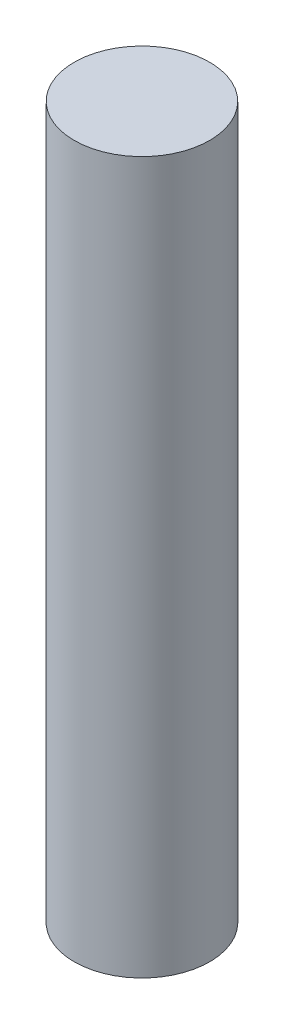
SolidWorks part; units mm, degrees
ref_plane "Front Plane" through (0, 0, 0) normal (0, 0, 1) x (1, 0, 0)
ref_plane "Top Plane" through (0, 0, 0) normal (0, 1, 0) x (1, 0, 0)
ref_plane "Right Plane" through (0, 0, 0) normal (1, 0, 0) x (0, 0, -1)
sketch "Sketch1" plane through (0, 0, 0) normal (0, 1, 0) x (1, 0, 0)
  circle A0 centre (0, 0) radius 3.175
  dimension "D1" = 6.35
sketch "Sketch2" plane through (0, 0, 0) normal (1, 0, 0) x (0, 0, -1)
  line L0 (0, 0) -> (0, 33.3368)
  circle A0 centre (0, 0) radius 33.3368 construction
extrude "Boss-Extrude1" add sketch "Sketch1" along normal up to vertex (33.3368 mm away) contours A0 up to point (0, 33.3368, 0)
